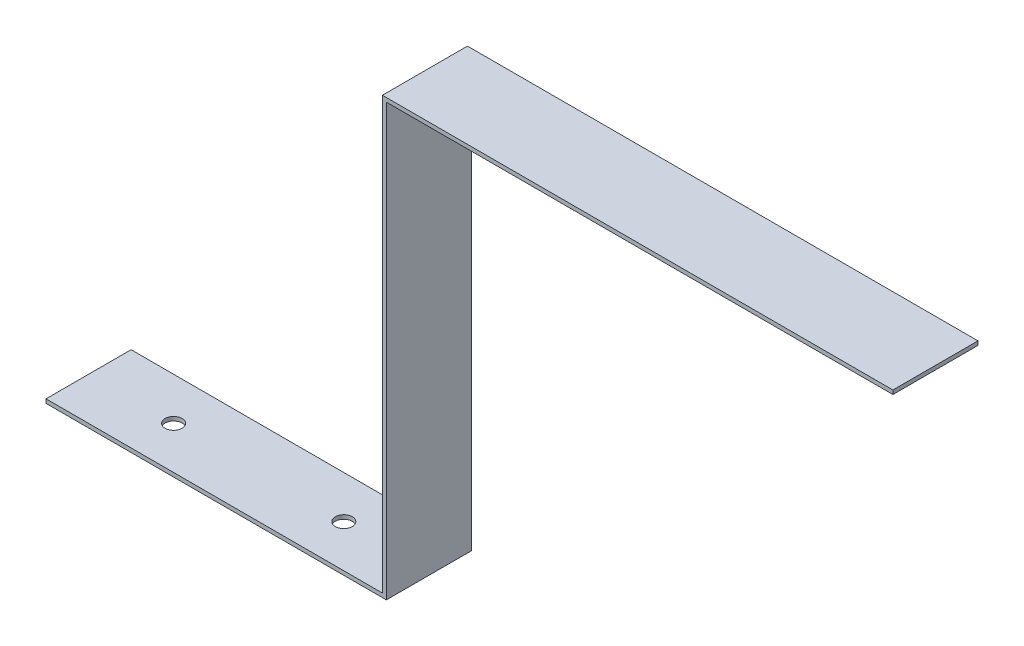
SolidWorks part; units mm, degrees
ref_plane "Front Plane" through (0, 0, 0) normal (0, 0, 1) x (1, 0, 0)
ref_plane "Top Plane" through (0, 0, 0) normal (0, 1, 0) x (1, 0, 0)
ref_plane "Right Plane" through (0, 0, 0) normal (1, 0, 0) x (0, 0, -1)
sketch "Sketch1" plane through (0, 0, 0) normal (0, 0, 1) x (1, 0, 0)
  line L0 (0, 0) -> (60, 0)
  line L1 (60, 0) -> (60, 76)
  line L2 (60, 76) -> (149.3, 76)
  line L3 (149.3, 76) -> (149.3, 76.7)
  line L4 (149.3, 76.7) -> (59.3, 76.7)
  line L5 (59.3, 76.7) -> (59.3, 0.7)
  line L6 (59.3, 0.7) -> (0, 0.7)
  line L7 (0, 0.7) -> (0, 0)
  dimension "D1" = 76
  dimension "D2" = 60
  dimension "D3" = 0.7
  dimension "D4" = 0.7
  dimension "D5" = 0.7
  dimension "D6" = 90
extrude "Boss-Extrude1" add sketch "Sketch1" along normal blind 15
sketch "Sketch2" plane through (0, 0.7, 0) normal (0, 1, 0) x (1, 0, 0)
  line L0 (0, -7.5) -> (59.3, -7.5) construction
  line L1 (0, -15) -> (0, 0) construction
  line L2 (59.3, -15) -> (59.3, 0) construction
  circle A0 centre (15, -7.5) radius 1.5
  circle A1 centre (45, -7.5) radius 1.5
  dimension "D1" = 3
  dimension "D2" = 15
  dimension "D4" = 30
extrude "Cut-Extrude1" cut sketch "Sketch2" against normal through all
